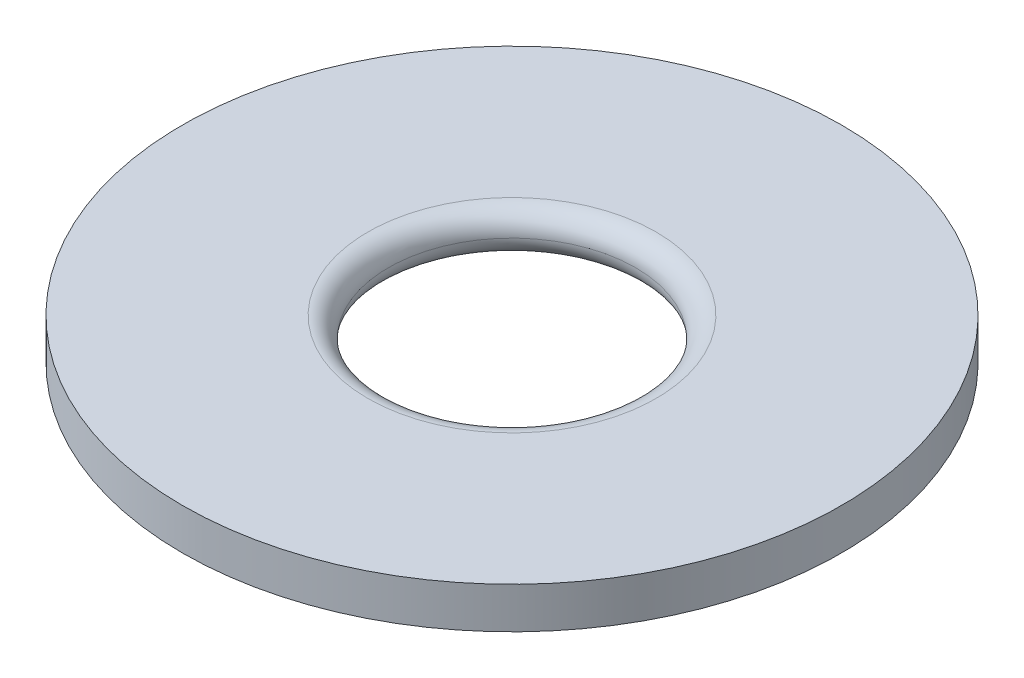
SolidWorks part; units mm, degrees
ref_plane "Front Plane" through (0, 0, 0) normal (0, 0, 1) x (1, 0, 0)
ref_plane "Top Plane" through (0, 0, 0) normal (0, 1, 0) x (1, 0, 0)
ref_plane "Right Plane" through (0, 0, 0) normal (1, 0, 0) x (0, 0, -1)
sketch "Sketch1" plane through (0, 0, 0) normal (0, 1, 0) x (1, 0, 0)
  circle A0 centre (0, 0) radius 6.35
  circle A1 centre (0, 0) radius 2.3813
  dimension "D1" = 4.7625
  dimension "D2" = 12.7
extrude "Boss-Extrude1" add sketch "Sketch1" along normal blind 0.7937
fillet "Fillet1" radius 0.3969 2 edges at (0, 0, 2.3813) (0, 0.7937, 2.3813)
